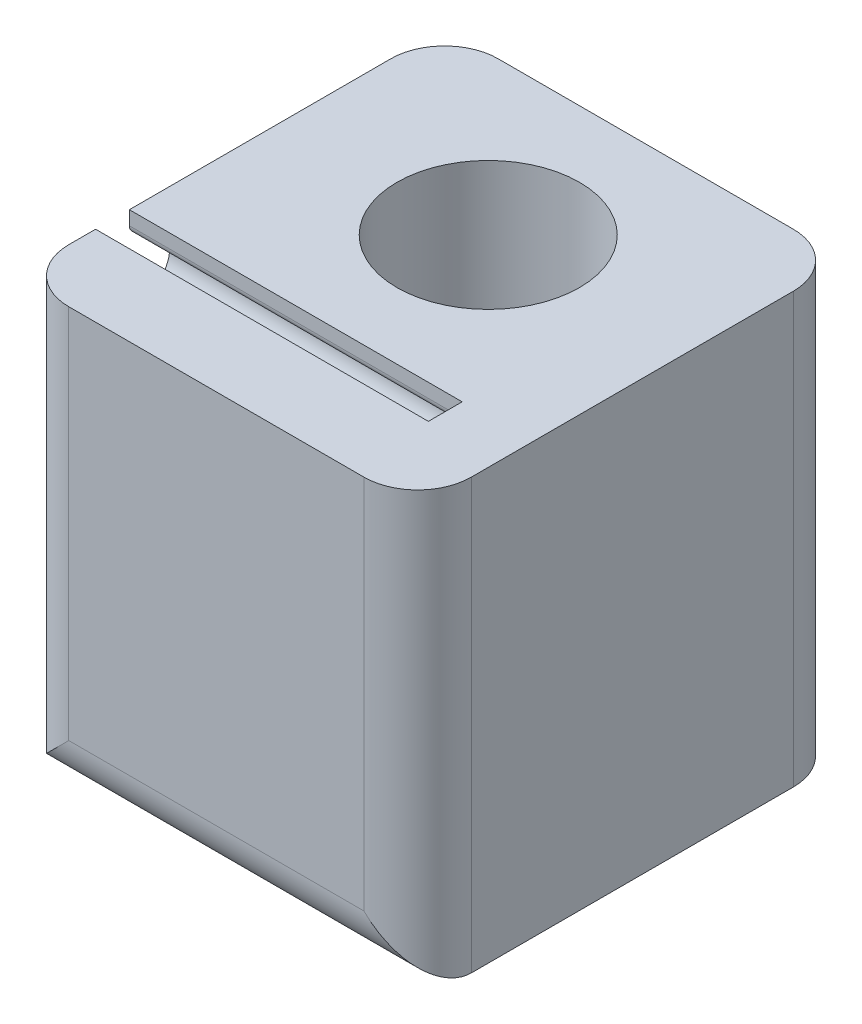
SolidWorks part; units mm, degrees
ref_plane "Front Plane" through (0, 0, 0) normal (0, 0, 1) x (1, 0, 0)
ref_plane "Top Plane" through (0, 0, 0) normal (0, 1, 0) x (1, 0, 0)
ref_plane "Right Plane" through (0, 0, 0) normal (1, 0, 0) x (0, 0, -1)
sketch "Sketch1" plane through (0, 0, 0) normal (1, 0, 0) x (0, 0, -1)
  line L1 (-4, -4) -> (4, -4)
  line L2 (-4, -4) -> (-4, 4)
  line L3 (-4, 4) -> (4, 4)
  line L4 (4, -4) -> (4, 4)
  line L5 (-4, -4) -> (4, 4) construction
  line L6 (-4, 4) -> (4, -4) construction
  point P0 (0, 0)
  dimension "D1" = 8
  dimension "D2" = 8
extrude "Boss-Extrude1" add sketch "Sketch1" along normal blind 7.5
sketch "Sketch2" plane through (0, 0, 0) normal (1, 0, 0) x (0, 0, -1)
  line L0 (-1.87, 4) -> (-1.87, 3.7402)
  line L1 (4, 4) -> (-4, 4) construction
  line L2 (-1.12, 3) -> (-1.87, 3) construction
  line L4 (-1.87, 2) -> (-1.87, 2.2598)
  line L5 (-2.5, 4) -> (-2.5, -4)
  line L6 (-4, -4) -> (4, -4) construction
  line L7 (-1.87, 4) -> (-2.5, 4)
  line L8 (-4, 4) -> (-4, -4) construction
  line L9 (-1.87, 2) -> (-1.87, 1.7402)
  line L10 (-1.87, 0) -> (-1.87, 0.2598)
  line L11 (-1.12, 1) -> (-1.87, 1) construction
  line L12 (-1.87, 0) -> (-1.87, -0.2598)
  line L13 (-1.87, -2) -> (-1.87, -1.7402)
  line L14 (-1.12, -1) -> (-1.87, -1) construction
  line L15 (-1.87, -2) -> (-1.87, -2.2598)
  line L16 (-1.87, -4) -> (-1.87, -3.7402)
  line L17 (-1.12, -3) -> (-1.87, -3) construction
  line L18 (-1.87, -4) -> (-2.5, -4)
  arc A0 (-1.87, 3.7402) -> (-1.7396, 3.5915) centre (-1.72, 3.7402) ccw
  arc A1 (-1.7396, 3.5915) -> (-1.4318, 3.4989) centre (-1.87, 2.6) cw
  arc A2 (-1.4318, 3.4989) -> (-1.4318, 2.5011) centre (-1.675, 3) cw
  arc A3 (-1.87, 2.2598) -> (-1.7396, 2.4085) centre (-1.72, 2.2598) cw
  arc A4 (-1.7396, 2.4085) -> (-1.4318, 2.5011) centre (-1.87, 3.4) ccw
  arc A5 (-1.87, 1.7402) -> (-1.7396, 1.5915) centre (-1.72, 1.7402) ccw
  arc A6 (-1.7396, 1.5915) -> (-1.4318, 1.4989) centre (-1.87, 0.6) cw
  arc A7 (-1.4318, 1.4989) -> (-1.4318, 0.5011) centre (-1.675, 1) cw
  arc A8 (-1.87, 0.2598) -> (-1.7396, 0.4085) centre (-1.72, 0.2598) cw
  arc A9 (-1.7396, 0.4085) -> (-1.4318, 0.5011) centre (-1.87, 1.4) ccw
  arc A10 (-1.87, -0.2598) -> (-1.7396, -0.4085) centre (-1.72, -0.2598) ccw
  arc A11 (-1.7396, -0.4085) -> (-1.4318, -0.5011) centre (-1.87, -1.4) cw
  arc A12 (-1.4318, -0.5011) -> (-1.4318, -1.4989) centre (-1.675, -1) cw
  arc A13 (-1.87, -1.7402) -> (-1.7396, -1.5915) centre (-1.72, -1.7402) cw
  arc A14 (-1.7396, -1.5915) -> (-1.4318, -1.4989) centre (-1.87, -0.6) ccw
  arc A15 (-1.87, -2.2598) -> (-1.7396, -2.4085) centre (-1.72, -2.2598) ccw
  arc A16 (-1.7396, -2.4085) -> (-1.4318, -2.5011) centre (-1.87, -3.4) cw
  arc A17 (-1.4318, -2.5011) -> (-1.4318, -3.4989) centre (-1.675, -3) cw
  arc A18 (-1.87, -3.7402) -> (-1.7396, -3.5915) centre (-1.72, -3.7402) cw
  arc A19 (-1.7396, -3.5915) -> (-1.4318, -3.4989) centre (-1.87, -2.6) ccw
  dimension "D1" = 0.555
  dimension "D2" = 1
  dimension "D3" = 0.15
  dimension "D4" = 0.75
  dimension "D5" = 0.4
  dimension "D6" = 1
  dimension "D7" = 0.63
  dimension "D8" = 1.5
  dimension "D10" = 2
  dimension "D9" = 4
extrude "Cut-Extrude1" cut sketch "Sketch2" along normal blind 6.2
hole_wizard "M3 Clearance Hole1" positions "Sketch5" profile "Sketch4" hole size "M3" standard "ANSI Metric" end condition through all
sketch "Sketch5" plane through (0, 4, 0) normal (0, 1, 0) x (1, 0, 0)
  line L0 (0, 4) -> (0, -1.87) construction
  line L1 (7.5, 4) -> (0, 4) construction
  point P0 (3.75, 1.065)
  point P9 (3.75, 4)
  point P10 (0, 1.065)
sketch "Sketch4" plane through (3.75, 4, -1.065) normal (1, 0, 0) x (0, 0, 1)
  line L0 (0, 0) -> (0, 8)
  line L1 (0, 8) -> (1.7, 8)
  line L2 (1.7, 8) -> (1.7, 0)
  line L5 (1.7, 0) -> (0, 0)
  line L11 (0, -6.35) -> (0, 107.95) construction
  dimension "Thru Hole Dia." = 3.4
  dimension "Thru Hole Depth" = 8
fillet "Fillet1" radius 1 5 edges at (3.75, -4, 4) (7.5, 0, 4) (7.5, 0, -4) (0, 0, -4) (0, 0, 4)
